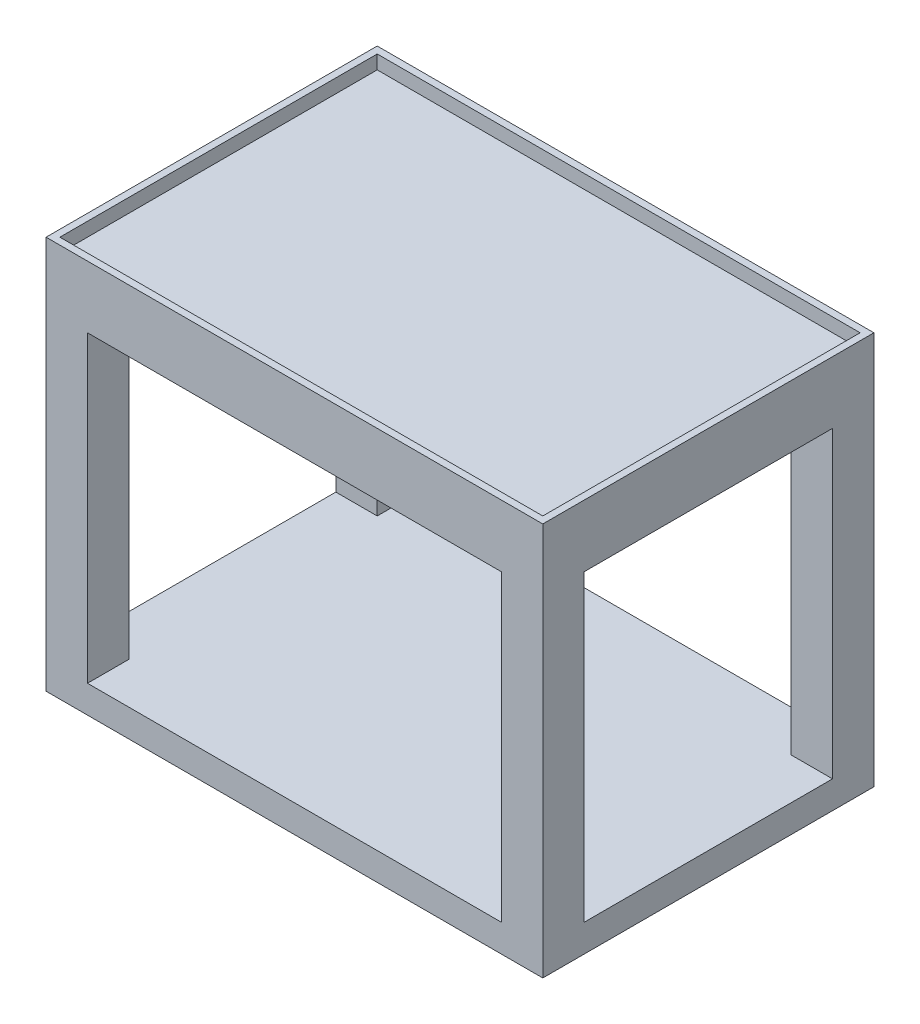
SolidWorks part; units mm, degrees
ref_plane "Front Plane" through (0, 0, 0) normal (0, 0, 1) x (1, 0, 0)
ref_plane "Top Plane" through (0, 0, 0) normal (0, 1, 0) x (1, 0, 0)
ref_plane "Right Plane" through (0, 0, 0) normal (1, 0, 0) x (0, 0, -1)
sketch "Sketch1" plane through (0, 0, 0) normal (0, 1, 0) x (1, 0, 0)
  line L1 (457.2, -304.8) -> (-457.2, -304.8)
  line L2 (457.2, -304.8) -> (457.2, 304.8)
  line L3 (457.2, 304.8) -> (-457.2, 304.8)
  line L4 (-457.2, -304.8) -> (-457.2, 304.8)
  line L5 (457.2, -304.8) -> (-457.2, 304.8) construction
  line L6 (457.2, 304.8) -> (-457.2, -304.8) construction
  point P0 (0, 0)
  dimension "D1" = 914.4
  dimension "D2" = 609.6
extrude "Boss-Extrude1" add sketch "Sketch1" along normal blind 114.3
sketch "Sketch2" plane through (0, 114.3, 0) normal (0, 1, 0) x (1, 0, 0)
  line L8 (-444.5, 292.1) -> (-444.5, -292.1)
  line L9 (-444.5, -292.1) -> (444.5, -292.1)
  line L10 (444.5, -292.1) -> (444.5, 292.1)
  line L11 (444.5, 292.1) -> (-444.5, 292.1)
  line L12 (-444.5, 292.1) -> (-444.5, -292.1)
  line L13 (-444.5, -292.1) -> (444.5, -292.1)
  line L14 (444.5, -292.1) -> (444.5, 292.1)
  line L15 (444.5, 292.1) -> (-444.5, 292.1)
  dimension "D1" = 12.7
extrude "Cut-Extrude1" cut sketch "Sketch2" against normal offset from surface (25.4 mm away) 88.9 up to face at (0, 0, 0)
sketch "Sketch3" plane through (0, 0, 0) normal (0, -1, 0) x (1, 0, 0)
  line L0 (0, -55) -> (0, 55) construction
  line L1 (-457.2, 304.8) -> (-381, 304.8)
  line L2 (-457.2, 304.8) -> (-457.2, 228.6)
  line L3 (-457.2, 228.6) -> (-381, 228.6)
  line L4 (-381, 304.8) -> (-381, 228.6)
  line L5 (457.2, 304.8) -> (457.2, 228.6)
  line L6 (457.2, 228.6) -> (381, 228.6)
  line L7 (381, 304.8) -> (381, 228.6)
  line L8 (457.2, 304.8) -> (381, 304.8)
  line L9 (55, 0) -> (-55, 0) construction
  line L10 (457.2, -304.8) -> (381, -304.8)
  line L11 (381, -304.8) -> (381, -228.6)
  line L12 (457.2, -228.6) -> (381, -228.6)
  line L13 (457.2, -304.8) -> (457.2, -228.6)
  line L14 (-381, -304.8) -> (-381, -228.6)
  line L15 (-457.2, -228.6) -> (-381, -228.6)
  line L16 (-457.2, -304.8) -> (-457.2, -228.6)
  line L17 (-457.2, -304.8) -> (-381, -304.8)
  point P5 (-374.4655, 228.6)
  dimension "D1" = 76.2
extrude "Boss-Extrude2" add sketch "Sketch3" along normal blind 609.6
sketch "Sketch4" plane through (0, -609.6, 0) normal (0, -1, 0) x (1, 0, 0)
  line L1 (-457.2, 304.8) -> (457.2, 304.8)
  line L2 (-457.2, 304.8) -> (-457.2, -304.8)
  line L3 (-457.2, -304.8) -> (457.2, -304.8)
  line L4 (457.2, 304.8) -> (457.2, -304.8)
extrude "Boss-Extrude3" add sketch "Sketch4" against normal blind 50.8
